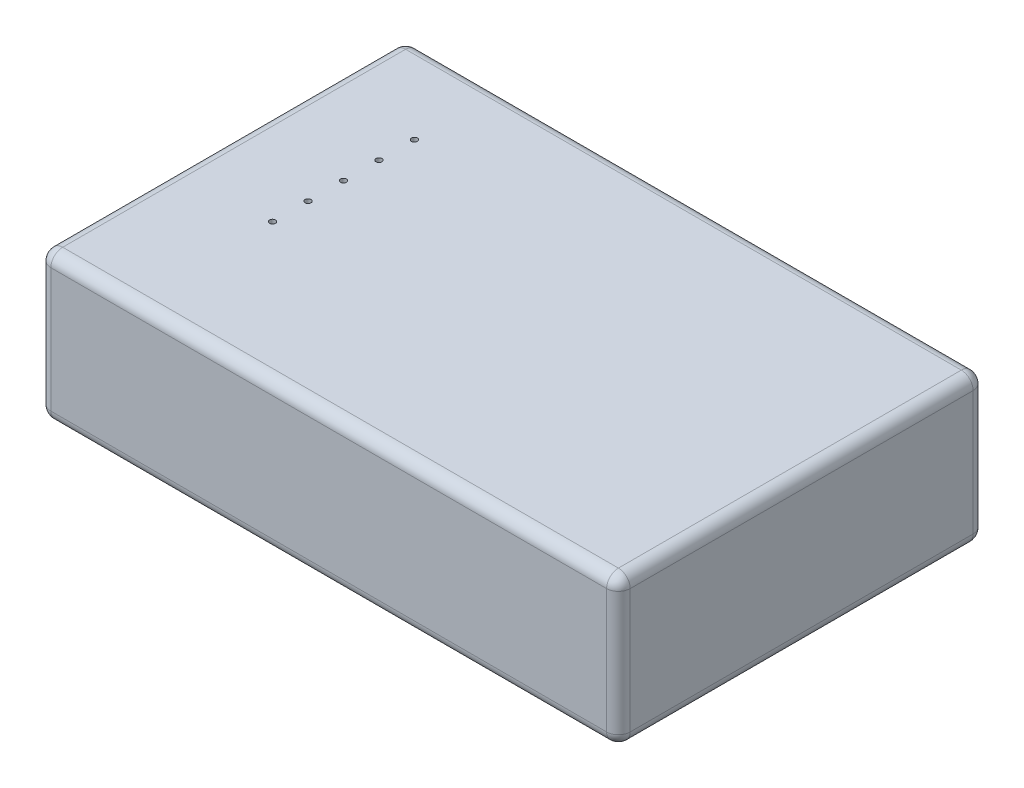
SolidWorks part; units mm, degrees
ref_plane "Front Plane" through (0, 0, 0) normal (0, 0, 1) x (1, 0, 0)
ref_plane "Top Plane" through (0, 0, 0) normal (0, 1, 0) x (1, 0, 0)
ref_plane "Right Plane" through (0, 0, 0) normal (1, 0, 0) x (0, 0, -1)
sketch "Sketch2" plane through (0, 0, 0) normal (0, 1, 0) x (1, 0, 0)
  line L1 (-49, -31) -> (49, -31)
  line L2 (-49, -31) -> (-49, 31)
  line L3 (-49, 31) -> (49, 31)
  line L4 (49, -31) -> (49, 31)
  line L5 (-49, -31) -> (49, 31) construction
  line L6 (-49, 31) -> (49, -31) construction
  point P0 (0, 0)
  dimension "D1" = 98
  dimension "D2" = 62
extrude "Boss-Extrude1" add sketch "Sketch2" along normal blind 25 contours L2 L1 L4 L3
sketch "Sketch3" plane through (-49, 0, 0) normal (-1, 0, 0) x (0, 0, 1)
  line L0 (31, 25) -> (-31, 25) construction
  line L1 (-13.907, 21) -> (-23.407, 21)
  line L2 (-13.907, 21) -> (-13.907, 9)
  line L3 (-13.907, 9) -> (-23.407, 9)
  line L4 (-23.407, 21) -> (-23.407, 9)
  line L5 (-13.907, 21) -> (-23.407, 9) construction
  line L6 (-13.907, 9) -> (-23.407, 21) construction
  point P0 (-18.657, 15)
  dimension "D1" = 4
  dimension "D2" = 12
  dimension "D3" = 9.5
extrude "Boss-Extrude4" add sketch "Sketch3" against normal blind 1 contours L2 L1 L4 L3
extrude "Cut-Extrude1" cut sketch "Sketch3<5>" against normal blind 1
sketch "Sketch3<5>" plane through (-49, 0, 0) normal (-1, 0, 0) x (0, 0, 1) same geometry as "Sketch3"
sketch "Sketch4" plane through (-48, 0, 0) normal (-1, 0, 0) x (0, 0, 1)
  line L0 (-13.907, 21) -> (-23.407, 21) construction
  line L1 (-23.407, 21) -> (-23.407, 9) construction
  circle A0 centre (-18.407, 16) radius 3.25
  dimension "D1" = 6.5
  dimension "D2" = 5
  dimension "D3" = 5
extrude "Cut-Extrude2" cut sketch "Sketch4" against normal blind 10
sketch "Sketch5" plane through (-38, 0, 0) normal (-1, 0, 0) x (0, 0, 1)
  circle A0 centre (-18.407, 16) radius 0.5
  dimension "D1" = 1
extrude "Boss-Extrude5" add sketch "Sketch5" along normal blind 8
sketch "Sketch6" plane through (-49, 0, 0) normal (-1, 0, 0) x (0, 0, 1)
  line L0 (-13.907, 9) -> (-13.907, 21) construction
  line L1 (-9.907, 21) -> (-2.907, 21)
  line L2 (-9.907, 21) -> (-9.907, 7)
  line L3 (-9.907, 7) -> (-2.907, 7)
  line L4 (-2.907, 21) -> (-2.907, 7)
  line L5 (-9.907, 21) -> (-2.907, 7) construction
  line L6 (-9.907, 7) -> (-2.907, 21) construction
  line L11 (31, 25) -> (-31, 25) construction
  point P0 (-6.407, 14)
  dimension "D1" = 4
  dimension "D2" = 7
  dimension "D3" = 14
  dimension "D4" = 4
extrude "Cut-Extrude9" cut sketch "Sketch6" against normal blind 10
sketch "Sketch7" plane through (-39, 0, 0) normal (-1, 0, 0) x (0, 0, 1)
  line L0 (-2.907, 21) -> (-9.907, 21) construction
  line L1 (-5.4664, 19) -> (-3.907, 19)
  line L2 (-5.4664, 19) -> (-5.4664, 9)
  line L3 (-5.4664, 9) -> (-3.907, 9)
  line L4 (-3.907, 19) -> (-3.907, 9)
  line L5 (-9.907, 7) -> (-2.907, 7) construction
  line L6 (-2.907, 7) -> (-2.907, 21) construction
  dimension "D1" = 2
  dimension "D2" = 2
  dimension "D3" = 1
extrude "Boss-Extrude6" add sketch "Sketch7" along normal blind 9
sketch "Sketch8" plane through (-49, 0, 0) normal (-1, 0, 0) x (0, 0, 1)
  line L0 (31, 25) -> (-31, 25) construction
  line L1 (19.593, 20) -> (4.593, 20)
  line L2 (19.593, 20) -> (19.593, 10)
  line L3 (19.593, 10) -> (4.593, 10)
  line L4 (4.593, 20) -> (4.593, 10)
  line L5 (-2.907, 7) -> (-2.907, 21) construction
  dimension "D1" = 5
  dimension "D2" = 10
  dimension "D3" = 15
  dimension "D4" = 7.5
extrude "Boss-Extrude7" add sketch "Sketch8" along normal blind 2 draft 30
ref_plane "Plane2" through (0, 12, 0) normal (0, -1, 0) x (-1, 0, 0)
sketch "Sketch9" plane through (0, 12, 0) normal (0, -1, 0) x (-1, 0, 0)
  line L0 (51, -5.7477) -> (51, -18.4383) construction
  line L1 (51, -7.6447) -> (51, -16.8055)
  spline S0 degree 2 poles (51, -7.6447) (51.419, -11.6679) (53.8134, -15.0002) knots 0 0 0 1 1 1
  spline S1 degree 2 poles (53.8134, -15.0002) (53.1044, -16.8217) (51, -16.8055) knots 0 0 0 1 1 1
extrude "Boss-Extrude8" add sketch "Sketch9" against normal blind 6
fillet "Fillet5" radius 2 12 edges at (49, 12.5, -31) (0, 25, -31) (-49, 12.5, -31) (0, 0, -31) (-49, 0, 0) (-49, 12.5, 31) (0, 0, 31) (49, 0, 0) (49, 25, 0) (49, 12.5, 31) (-49, 25, 0) (0, 25, 31)
sketch "Sketch10" plane through (0, 0, 0) normal (0, -1, 0) x (1, 0, 0)
  line L0 (-47, -29) -> (47, -29) construction
  line L1 (47, 29) -> (-47, 29) construction
  line L2 (47, -29) -> (47, 29) construction
  line L3 (-47, 29) -> (-47, -29) construction
  circle A0 centre (-43, -25.5) radius 2.5
  circle A1 centre (-43, 25.5) radius 2.5
  circle A2 centre (43, 25.5) radius 2.5
  circle A3 centre (43, -25.5) radius 2.5
  dimension "D1" = 5
  dimension "D2" = 5
  dimension "D3" = 5
  dimension "D4" = 5
  dimension "D5" = 3.5
  dimension "D6" = 3.5
  dimension "D7" = 3.5
  dimension "D8" = 3.5
  dimension "D9" = 4
  dimension "D10" = 4
  dimension "D11" = 4
  dimension "D12" = 4
extrude "Cut-Extrude10" cut sketch "Sketch10" against normal blind 6
sketch "Sketch11" plane through (0, 25, 0) normal (0, 1, 0) x (1, 0, 0)
  line L0 (47, 29) -> (-47, 29) construction
  line L1 (-47, 29) -> (-47, -29) construction
  circle A0 centre (-33, 16.5) radius 0.5
  circle A1 centre (-33, 10.5) radius 0.5
  circle A2 centre (-33, 4.5) radius 0.5
  circle A3 centre (-33, -1.5) radius 0.5
  circle A4 centre (-33, -7.5) radius 0.5
  dimension "D1" = 1
  dimension "D2" = 1
  dimension "D3" = 1
  dimension "D4" = 1
  dimension "D5" = 1
  dimension "D6" = 12.5
  dimension "D7" = 6
  dimension "D8" = 6
  dimension "D9" = 6
  dimension "D10" = 6
  dimension "D11" = 14
extrude "Cut-Extrude11" cut sketch "Sketch11" against normal blind 3
